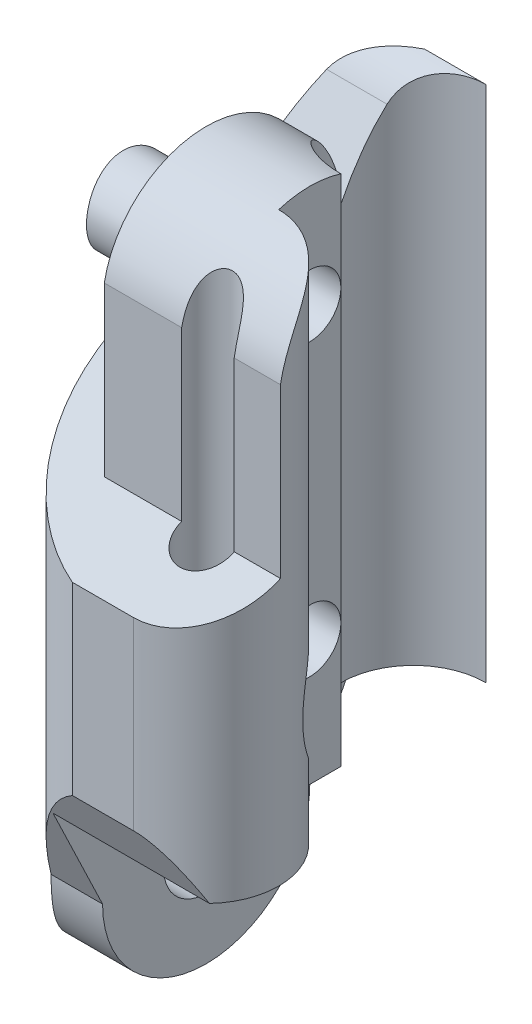
SolidWorks part; units mm, degrees
ref_plane "Front Plane" through (0, 0, 0) normal (0, 0, 1) x (1, 0, 0)
ref_plane "Top Plane" through (0, 0, 0) normal (0, 1, 0) x (1, 0, 0)
ref_plane "Right Plane" through (0, 0, 0) normal (1, 0, 0) x (0, 0, -1)
sketch "Sketch1" plane through (0, 0, 0) normal (0, 1, 0) x (1, 0, 0)
  line L0 (-2.958, 8.5) -> (2.958, 8.5)
  line L1 (-2.958, -8.5) -> (2.958, -8.5)
  arc A0 (-2.958, 8.5) -> (-2.958, -8.5) centre (0, 0) ccw
  arc A1 (2.958, 8.5) -> (2.958, -8.5) centre (0, 0) cw
  point P9 (-9, 0)
  point P10 (9, 0)
  dimension "D1" = 18
  dimension "D2" = 17
extrude "Boss-Extrude1" add sketch "Sketch1" along normal blind 35
sketch "Sketch2" plane through (0, 0, 0) normal (0, -1, 0) x (1, 0, 0)
  circle A0 centre (0, -5) radius 1.27
  circle A1 centre (0, 5) radius 1.27
  dimension "D1" = 2.54
  dimension "D2" = 5
  dimension "D3" = 5
extrude "Cut-Extrude1" cut sketch "Sketch2" against normal blind 35
sketch "Sketch3" plane through (0, 0, -8.5) normal (0, 0, -1) x (-1, 0, 0)
  line L0 (5, 0) -> (5, 10)
  line L1 (5, 10) -> (-5, 10)
  line L2 (-5, 10) -> (-5, 0)
  line L3 (5, 0) -> (-5, 0)
  line L4 (-2.958, 0) -> (2.958, 0) construction
  point P10 (0, 0)
  dimension "D1" = 10
  dimension "D2" = 10
extrude "Cut-Extrude2" cut sketch "Sketch3" against normal up to surface (17 mm away) up to face at (0, 17.5, 8.5)
sketch "Sketch4" plane through (5, 0, 0) normal (-1, 0, 0) x (0, 0, 1)
  line L0 (-7.4833, 10) -> (-5, 5)
  line L1 (8.5, 12.3086) -> (5, 5)
  line L2 (7.4833, 0) -> (-7.4833, 0) construction
  line L3 (-7.4833, 10) -> (-9.8579, -1.8222)
  line L4 (-9.8579, -1.8222) -> (9.8579, -1.8222)
  line L6 (8.5, 35) -> (8.5, 10) construction
  line L7 (9.8579, -1.8222) -> (8.5, 12.3086)
  arc A0 (-5, 5) -> (5, 5) centre (0, 5) ccw
  circle A1 centre (0, 5) radius 2.05
  point P7 (0, 0)
  dimension "D1" = 4.1
  dimension "D2" = 5
  dimension "D3" = 12.0584
  dimension "D4" = 37.769
extrude "Cut-Extrude3" cut sketch "Sketch4" against normal mid plane 35
ref_plane "Plane1" through (-2.958, 0, 0) normal (-1, 0, 0) x (0, 0, 1)
sketch "Sketch6" plane through (-2.958, 0, 0) normal (-1, 0, 0) x (0, 0, 1)
  line L0 (8.5, 21.2199) -> (0, 25)
  line L1 (8.5, 35) -> (8.5, 12.3086) construction
  line L2 (-5, 30) -> (-6.7559, 33.5353)
  line L3 (8.5, 35) -> (-8.5, 35) construction
  line L4 (8.5, 21.2199) -> (17.803, 42.886)
  line L6 (-7.4833, 10) -> (-5, 5) construction
  line L7 (-8.5, 35) -> (17.803, 42.886)
  arc A0 (0, 25) -> (-5, 30) centre (0, 30) cw
  circle A1 centre (0, 30) radius 2
  arc A2 (-6.7559, 33.5353) -> (-8.5, 35) centre (-9.3069, 32.2683) ccw
  dimension "D1" = 5
  dimension "D3" = 4
  dimension "D2" = 5
  dimension "D4" = 8.5
extrude "Cut-Extrude5" cut sketch "Sketch6" against normal blind 9.6 from surface starting at face at (5, 7.05, 0)
sketch "Sketch7" plane through (5, 0, 0) normal (1, 0, 0) x (0, 0, -1)
  line L0 (5, 30) -> (6.7559, 33.5353)
  line L2 (-8.3419, 47.5367) -> (-13.1682, 33.5285)
  line L3 (-7.4833, 35) -> (7.4833, 35) construction
  line L4 (-4.9155, 30.9155) -> (-4.9155, 22.814)
  line L5 (-7.4833, 21.6721) -> (0, 25) construction
  line L6 (-4.9155, 22.814) -> (-10.0468, 20.532)
  line L7 (-10.0468, 20.532) -> (-13.1682, 33.5285)
  line L8 (6.7559, 33.5353) -> (5, 30) construction
  line L9 (8.5, 35) -> (-8.3419, 47.5367)
  arc A0 (5, 30) -> (-4.9155, 30.9155) centre (0, 30) ccw
  arc A1 (6.7559, 33.5353) -> (8.5, 35) centre (9.3069, 32.2683) cw
  arc A2 (7.4833, 34.4564) -> (6.7559, 33.5353) centre (9.3069, 32.2683) ccw construction
  dimension "D1" = 5
fillet "Fillet3" radius 1 2 edges at (0, 10, -3.73) (0, 10, 6.27)
extrude "Cut-Extrude6" cut sketch "Sketch6<3>" along normal blind 6.604 from surface starting at face at (-5, 2.95, 0)
sketch "Sketch6<3>" plane through (-2.958, 0, 0) normal (-1, 0, 0) x (0, 0, 1) same geometry as "Sketch6"
extrude "Cut-Extrude7" cut sketch "Sketch7" against normal blind 14.986
sketch "Sketch8" plane through (0, 10, 0) normal (0, -1, 0) x (1, 0, 0)
  line L0 (0, 1.5) -> (0, -1.5)
  line L1 (-2.958, -8.5) -> (2.958, -8.5) construction
  line L2 (2.958, 8.5) -> (-2.958, 8.5) construction
  line L3 (0, 8.5) -> (-4.7901, 15.219)
  line L4 (-4.7901, 15.219) -> (34.9648, -1.5)
  line L5 (34.9648, -1.5) -> (-4.7901, -16.0136)
  line L6 (-4.7901, -16.0136) -> (0, -8.5)
  arc A0 (0, -1.5) -> (0, -8.5) centre (0, -5) ccw
  arc A1 (0, 1.5) -> (0, 8.5) centre (0, 5) ccw
  circle A2 centre (0, 5) radius 2.27 construction
  circle A3 centre (0, -5) radius 2.27 construction
  point P9 (0, 0)
  point P18 (34.9648, -1.5)
extrude "Cut-Extrude8" cut sketch "Sketch8" against normal mid plane 62.992
sketch "Sketch9" plane through (0, 0, 0) normal (1, 0, 0) x (0, 0, -1)
  line L1 (1.5, 10) -> (-1.5, 10) construction
  circle A0 centre (0, 16) radius 1.5
  dimension "D2" = 3
  dimension "D1" = 6
extrude "Cut-Extrude9" cut sketch "Sketch9" against normal blind 14.224
sketch "Sketch13" plane through (0, 0, 0) normal (1, 0, 0) x (0, 0, -1)
  line L1 (1.5, 34.7697) -> (1.5, 16) construction
  circle A0 centre (0, 30) radius 1.5
  circle A2 centre (0, 30) radius 2 construction
sketch "Sketch14" plane through (0, 0, 0) normal (1, 0, 0) x (0, 0, -1)
  line L0 (0, 12.5) -> (0, 19.5)
  arc A0 (0, 19.5) -> (0, 12.5) centre (0, 16) ccw
  arc A1 (-1.5, 16) -> (1.5, 16) centre (0, 16) ccw construction
  dimension "D1" = 3.5
extrude "Cut-Extrude11" cut sketch "Sketch14" along normal blind 6.048
extrude "Cut-Extrude12" cut sketch "Sketch13" against normal blind 3
sketch "Sketch15" plane through (0, 0, 0) normal (1, 0, 0) x (0, 0, -1)
  circle A0 centre (0, 16) radius 2.75
  dimension "D1" = 5.5
extrude "Cut-Extrude13" cut sketch "Sketch15" against normal blind 7.572 from offset 5.5 offset against normal yes
